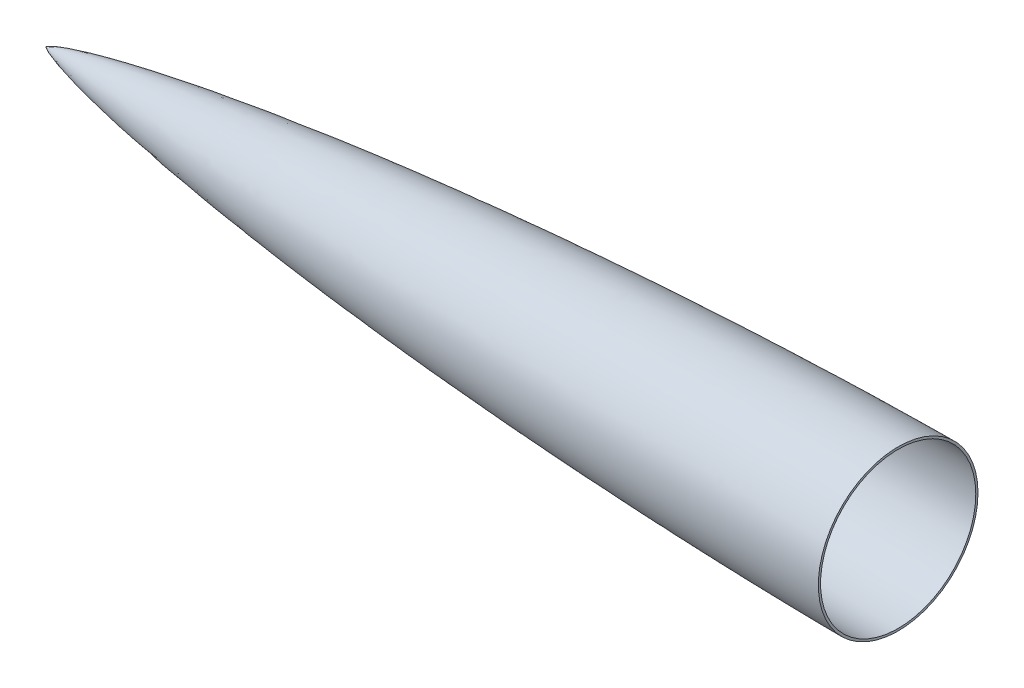
SolidWorks part; units mm, degrees
ref_plane "Front Plane" through (0, 0, 0) normal (0, 0, 1) x (1, 0, 0)
ref_plane "Top Plane" through (0, 0, 0) normal (0, 1, 0) x (1, 0, 0)
ref_plane "Right Plane" through (0, 0, 0) normal (1, 0, 0) x (0, 0, -1)
sketch "Sketch2" plane through (0, 0, 0) normal (0, 1, 0) x (1, 0, 0)
  line L0 (838, 78.5) -> (838, 0)
  line L1 (838, 0) -> (0, 0)
  spline S0 degree 4 poles (0, 0) (0.0026, 0.0086) (0.009, 0.0252) (0.0271, 0.0559) (0.0704, 0.1126) (0.1373, 0.1841) (0.2291, 0.2685) (0.4079, 0.4151) (0.6191, 0.565) (0.8596, 0.7205) (1.2263, 0.9398) (1.719, 1.2127) (2.5681, 1.6415) (4.092, 2.3298) (6.7258, 3.3825) (11.4582, 5.0409) (19.8824, 7.6008) (33.9609, 11.2838) (52.5672, 15.4747) (74.6259, 19.8758) (105.4455, 25.4223) (142.8171, 31.3986) (187.4217, 37.6992) (239.2733, 44.1205) (291.2096, 49.8096) (343.2114, 54.8627) (395.2652, 59.3467) (447.3611, 63.3091) (499.4916, 66.7853) (551.6506, 69.8021) (603.8332, 72.3794) (656.035, 74.5309) (701.7252, 76.0472) (740.896, 77.0831) (773.4369, 77.7603) (796.133, 78.1303) (815.5126, 78.3649) (828.3624, 78.4648) (834.7874, 78.4959) (838, 78.5) knots 0 0 0 0 0 0.000042 0.000084 0.000169 0.000337 0.000506 0.000675 0.001264 0.001564 0.001863 0.002699 0.003933 0.006071 0.009786 0.016139 0.027694 0.047791 0.078745 0.106522 0.134299 0.196207 0.258114 0.320021 0.381928 0.443836 0.505743 0.56765 0.629557 0.691465 0.753372 0.815279 0.877186 0.90814 0.939094 0.969547 0.984773 1 1 1 1 1 construction
  spline S1 degree 4 poles (0, 0) (0.0026, 0.0086) (0.009, 0.0252) (0.0271, 0.0559) (0.0704, 0.1126) (0.1373, 0.1841) (0.2291, 0.2685) (0.4079, 0.4151) (0.6191, 0.565) (0.8596, 0.7205) (1.2263, 0.9398) (1.719, 1.2127) (2.5681, 1.6415) (4.092, 2.3298) (6.7258, 3.3825) (11.4582, 5.0409) (19.8824, 7.6008) (33.9609, 11.2838) (52.5672, 15.4747) (74.6259, 19.8758) (105.4455, 25.4223) (142.8171, 31.3986) (187.4217, 37.6992) (239.2733, 44.1205) (291.2096, 49.8096) (343.2114, 54.8627) (395.2652, 59.3467) (447.3611, 63.3091) (499.4916, 66.7853) (551.6506, 69.8021) (603.8332, 72.3794) (656.035, 74.5309) (701.7252, 76.0472) (740.896, 77.0831) (773.4369, 77.7603) (796.133, 78.1303) (815.5126, 78.3649) (828.3624, 78.4648) (834.7874, 78.4959) (838, 78.5) knots 0 0 0 0 0 0.000042 0.000084 0.000169 0.000337 0.000506 0.000675 0.001264 0.001564 0.001863 0.002699 0.003933 0.006071 0.009786 0.016139 0.027694 0.047791 0.078745 0.106522 0.134299 0.196207 0.258114 0.320021 0.381928 0.443836 0.505743 0.56765 0.629557 0.691465 0.753372 0.815279 0.877186 0.90814 0.939094 0.969547 0.984773 1 1 1 1 1
  dimension "D1" = 838
revolve "Revolve2" add sketch "Sketch2" angle 360 about L1
shell "Shell1" thickness 2.18 removed face at (838, 0, -78.5)
